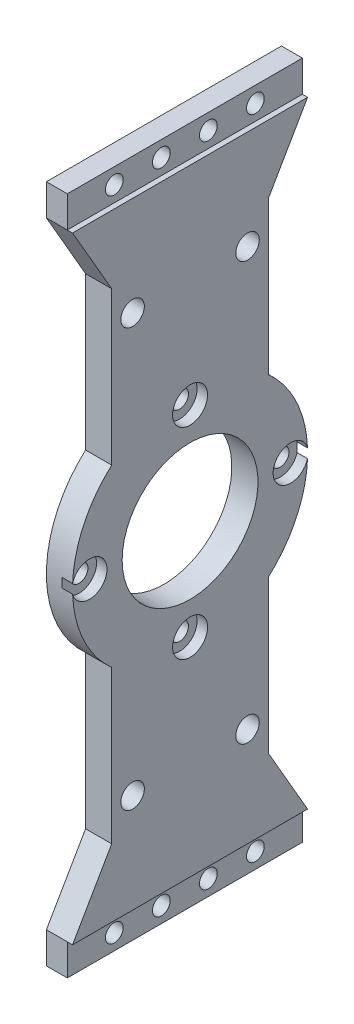
SolidWorks part; units mm, degrees
material "Сплав 2024"
ref_plane "Спереди" through (0, 0, 0) normal (0, 0, 1) x (1, 0, 0)
ref_plane "Сверху" through (0, 0, 0) normal (0, 1, 0) x (1, 0, 0)
ref_plane "Справа" through (0, 0, 0) normal (1, 0, 0) x (0, 0, -1)
sketch "Эскиз1" plane through (0, 0, 0) normal (0, 1, 0) x (1, 0, 0)
  line L1 (0, 0) -> (5, 0)
  line L2 (0, 0) -> (0, -30)
  line L3 (0, -30) -> (5, -30)
  line L4 (5, 0) -> (5, -30)
  dimension "D1" = 5
  dimension "D2" = 30
extrude "Бобышка-Вытянуть1" add sketch "Эскиз1" along normal blind 130
sketch "Эскиз2" plane through (0, 0, 0) normal (-1, 0, 0) x (0, 0, 1)
  line L0 (30, 65) -> (0, 65) construction
  line L1 (30, 130) -> (30, 0) construction
  line L2 (0, 130) -> (0, 0) construction
  line L3 (15, 130) -> (15, 0) construction
  line L4 (0, 130) -> (30, 130) construction
  line L5 (0, 0) -> (30, 0) construction
  circle A0 centre (15, 65) radius 22.5
  dimension "D1" = 45
extrude "Бобышка-Вытянуть2" add sketch "Эскиз2" against normal up to surface (5 mm away) up to face at (5, 65, 15)
sketch "Эскиз3" plane through (0, 0, 0) normal (-1, 0, 0) x (0, 0, 1)
  circle A0 centre (15, 65) radius 13
  dimension "D1" = 26
extrude "Вырез-Вытянуть1" cut sketch "Эскиз3" against normal through all
sketch "Эскиз4" plane through (5, 0, 0) normal (-1, 0, 0) x (0, 0, 1)
  line L0 (15, 87.5) -> (15, 42.5) construction
  line L1 (15, 130) -> (15, 0) construction
  line L2 (37.5, 65) -> (-7.5, 65) construction
  circle A0 centre (15, 65) radius 19.25 construction
  circle A1 centre (15, 65) radius 22.5 construction
  dimension "D1" = 38.5
hole_wizard "Цековка для  винта с полукруглой головкой M31" positions "Эскиз6" profile "Эскиз5" counterbore size "M3" standard "Ansi Metric" end condition through all
sketch "Эскиз6" plane through (5, -25.0247, 7.2629) normal (-1, 0, 0) x (0, 0, 1)
  line L0 (7.7371, 112.5247) -> (7.7371, 67.5247) construction
  line L1 (30.2371, 90.0247) -> (-14.7629, 90.0247) construction
  circle A0 centre (7.7371, 90.0247) radius 19.25 construction
  point P0 (7.7371, 109.2747)
  point P6 (-11.5129, 90.0247)
  point P10 (7.7371, 70.7747)
  point P12 (26.9871, 90.0247)
sketch "Эскиз5" plane through (5, 84.25, 15) normal (0, 1, 0) x (0, 0, -1)
  line L0 (0, 0) -> (0, 5)
  line L1 (0, 5) -> (1.7, 5)
  line L3 (1.7, 5) -> (1.7, 2)
  line L4 (1.7, 2) -> (3.35, 2)
  line L5 (3.35, 2) -> (3.35, 0)
  line L7 (3.35, 0) -> (0, 0)
  line L11 (0, -6.35) -> (0, 107.95) construction
  dimension "Диаметр сквозного отверстия" = 3.4
  dimension "Глубина сквозного отверстия" = 5
  dimension "Диаметр цековки" = 6.7
  dimension "Глубина цековки" = 2
sketch "Эскиз8" plane through (5, 0, 0) normal (1, 0, 0) x (0, 0, -1)
  line L0 (-15, 130) -> (-15, 0) construction
  line L1 (-30, 130) -> (0, 130) construction
  line L2 (-30, 0) -> (0, 0) construction
  line L3 (19.447, 65) -> (-49.447, 65) construction
  line L4 (0, 130) -> (0, 81.7705) construction
  line L5 (-26, 105) -> (-4, 105) construction
  line L6 (-26, 105) -> (-26, 25) construction
  line L7 (-26, 25) -> (-4, 25) construction
  line L8 (-4, 105) -> (-4, 25) construction
  line L9 (-26, 105) -> (-4, 25) construction
  line L10 (-26, 25) -> (-4, 105) construction
  point P8 (-15, 65)
  point P9 (-15, 65)
  dimension "D1" = 4
  dimension "D2" = 80
hole_wizard "Отверстие с зазором M41" positions "Эскиз10" profile "Эскиз9" hole size "M4" standard "Ansi Metric" end condition through all
sketch "Эскиз10" plane through (5, 0, 0) normal (1, 0, 0) x (0, 0, -1)
  point P0 (-26, 105)
  point P3 (-4, 105)
  point P6 (-4, 25)
  point P9 (-26, 25)
sketch "Эскиз9" plane through (5, 105, 26) normal (0, 1, 0) x (0, 0, -1)
  line L0 (0, 0) -> (0, 5)
  line L1 (0, 5) -> (2.25, 5)
  line L2 (2.25, 5) -> (2.25, 0)
  line L5 (2.25, 0) -> (0, 0)
  line L11 (0, -6.35) -> (0, 107.95) construction
  dimension "Диаметр сквозного отверстия" = 4.5
  dimension "Глубина сквозного отверстия" = 5
sketch "Эскиз11" plane through (5, 0, 0) normal (1, 0, 0) x (0, 0, -1)
  line L0 (-15, 130) -> (-15, 0) construction
  line L1 (-30, 130) -> (0, 130) construction
  line L2 (-30, 0) -> (0, 0) construction
  line L3 (-37.5, 124) -> (-30, 111.0096)
  line L4 (-37.5, 124) -> (7.5, 124) construction
  line L5 (-37.5, 124) -> (-37.5, 130)
  line L6 (-37.5, 130) -> (7.5, 130)
  line L7 (7.5, 124) -> (7.5, 130)
  line L8 (-37.5, 124) -> (7.5, 130) construction
  line L9 (-37.5, 130) -> (7.5, 124) construction
  line L10 (-30, 130) -> (-30, 81.7705) construction
  line L11 (-30, 111.0096) -> (0, 111.0096)
  line L12 (0, 130) -> (0, 81.7705) construction
  line L13 (0, 111.0096) -> (7.5, 124)
  line L14 (-37.5, 127) -> (7.5, 127) construction
  line L15 (-28.5, 130) -> (-28.5, 124) construction
  line L16 (-19.5, 130) -> (-19.5, 124) construction
  line L17 (-10.5, 130) -> (-10.5, 124) construction
  line L18 (-1.5, 130) -> (-1.5, 124) construction
  line L19 (-15, 65) -> (-5.455, 65) construction
  line L20 (-1.5, 0) -> (-1.5, 6) construction
  line L21 (-10.5, 0) -> (-10.5, 6) construction
  line L22 (-19.5, 0) -> (-19.5, 6) construction
  line L23 (-28.5, 0) -> (-28.5, 6) construction
  line L24 (-37.5, 3) -> (7.5, 3) construction
  line L25 (-37.5, 0) -> (7.5, 6) construction
  line L26 (-37.5, 6) -> (7.5, 0) construction
  line L27 (-37.5, 6) -> (7.5, 6) construction
  line L28 (0, 18.9904) -> (7.5, 6)
  line L29 (-30, 18.9904) -> (0, 18.9904)
  line L30 (7.5, 6) -> (7.5, 0)
  line L31 (-37.5, 0) -> (7.5, 0)
  line L32 (-37.5, 6) -> (-37.5, 0)
  line L33 (-37.5, 6) -> (-30, 18.9904)
  point P6 (-15, 127)
  point P45 (-15, 3)
  dimension "D1" = 6
  dimension "D2" = 45
  dimension "D3" = 120
  dimension "D4" = 9
  dimension "D5" = 9
  dimension "D6" = 9
  dimension "D7" = 9
extrude "Бобышка-Вытянуть3" add sketch "Эскиз11" against normal up to surface (5 mm away) up to face at (0, 105, 23.75)
hole_wizard "Отверстие с зазором M31" positions "Эскиз13" profile "Эскиз12" hole size "M3" standard "Ansi Metric" end condition through all
sketch "Эскиз13" plane through (5, 0, 0) normal (1, 0, 0) x (0, 0, -1)
  line L0 (-28.5, 130) -> (-28.5, 124) construction
  line L1 (-19.5, 130) -> (-19.5, 124) construction
  line L2 (-10.5, 130) -> (-10.5, 124) construction
  line L3 (-1.5, 130) -> (-1.5, 124) construction
  line L4 (-28.5, 0) -> (-28.5, 6) construction
  line L5 (-19.5, 0) -> (-19.5, 6) construction
  line L6 (-10.5, 0) -> (-10.5, 6) construction
  line L7 (-1.5, 0) -> (-1.5, 6) construction
  point P0 (-28.5, 127)
  point P4 (-19.5, 127)
  point P8 (-10.5, 127)
  point P12 (-1.5, 127)
  point P16 (-28.5, 3)
  point P20 (-19.5, 3)
  point P24 (-10.5, 3)
  point P28 (-1.5, 3)
sketch "Эскиз12" plane through (5, 127, 28.5) normal (0, 1, 0) x (0, 0, -1)
  line L0 (0, 0) -> (0, 5)
  line L1 (0, 5) -> (1.7, 5)
  line L2 (1.7, 5) -> (1.7, 0)
  line L5 (1.7, 0) -> (0, 0)
  line L11 (0, -6.35) -> (0, 107.95) construction
  dimension "Диаметр сквозного отверстия" = 3.4
  dimension "Глубина сквозного отверстия" = 5
sketch "Эскиз14" plane through (5, 0, 0) normal (1, 0, 0) x (0, 0, -1)
  line L1 (-37.5, 130) -> (7.5, 130)
  line L2 (-37.5, 130) -> (-37.5, 124)
  line L3 (-37.5, 124) -> (7.5, 124)
  line L4 (7.5, 130) -> (7.5, 124)
  line L5 (-37.5, 0) -> (7.5, 0)
  line L6 (-37.5, 0) -> (-37.5, 6)
  line L7 (-37.5, 6) -> (7.5, 6)
  line L8 (7.5, 0) -> (7.5, 6)
extrude "Вырез-Вытянуть2" cut sketch "Эскиз14" against normal blind 1
equation "\"D4@Эскиз11\"=\"D2@Эскиз11\"/5"
equation "\"D5@Эскиз11\"=\"D4@Эскиз11\""
equation "\"D6@Эскиз11\"=\"D4@Эскиз11\""
equation "\"D7@Эскиз11\"=\"D4@Эскиз11\""
